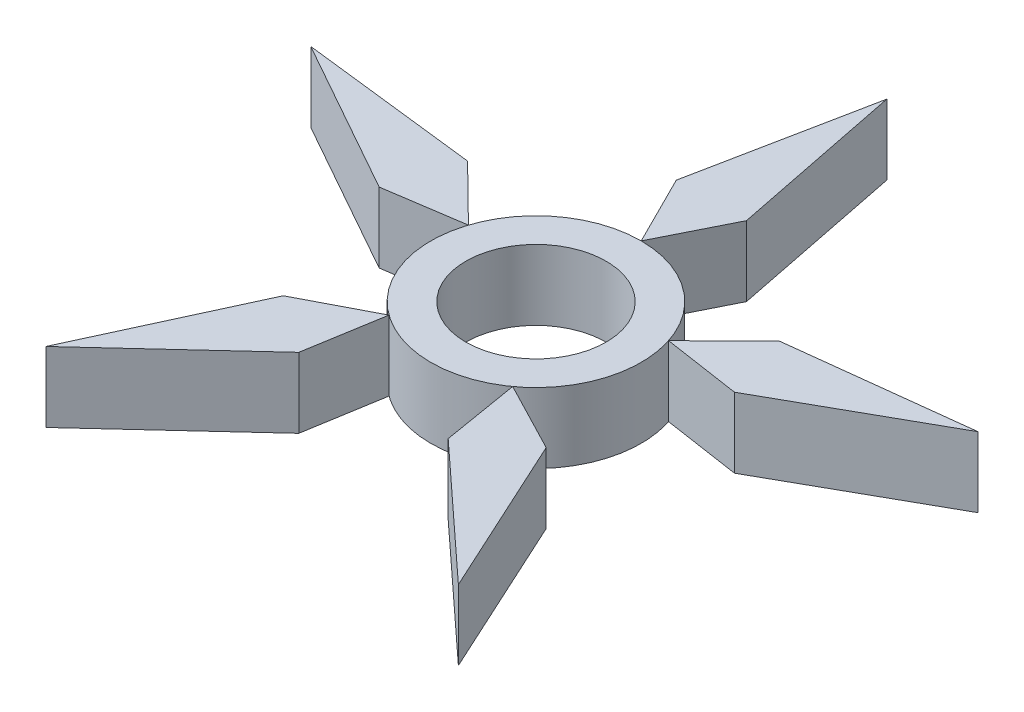
SolidWorks part; units mm, degrees
ref_plane "Front Plane" through (0, 0, 0) normal (0, 0, 1) x (1, 0, 0)
ref_plane "Top Plane" through (0, 0, 0) normal (0, 1, 0) x (1, 0, 0)
ref_plane "Right Plane" through (0, 0, 0) normal (1, 0, 0) x (0, 0, -1)
sketch "Sketch1" plane through (0, 0, 0) normal (0, 1, 0) x (1, 0, 0)
  circle A0 centre (0, 0) radius 1
  circle A2 centre (0, 0) radius 1.5
extrude "Boss-Extrude2" add sketch "Sketch1" along normal blind 1
sketch "Sketch2" plane through (0, 0, 0) normal (0, 1, 0) x (1, 0, 0)
  line L0 (0, 1.5) -> (-0.5, 2.5)
  line L1 (-0.5, 2.5) -> (0, 5)
  line L2 (0, 5) -> (0.5, 2.5)
  line L3 (0.5, 2.5) -> (0, 1.5)
  circle A1 centre (0, 0) radius 1.5 construction
  dimension "D1" = 3.5
  dimension "D2" = 0.5
  dimension "D3" = 0.5
  dimension "D4" = 1
  dimension "D5" = 1
extrude "Boss-Extrude3" add sketch "Sketch2" along normal blind 1 separate body
ref_axis "Axis1" through (0, 1, 0) along (0, -1, 0)
pattern_circular "CirPattern9" count 5 over 360 about axis through (0, 1, 0) along (0, -1, 0) of bodies 104
